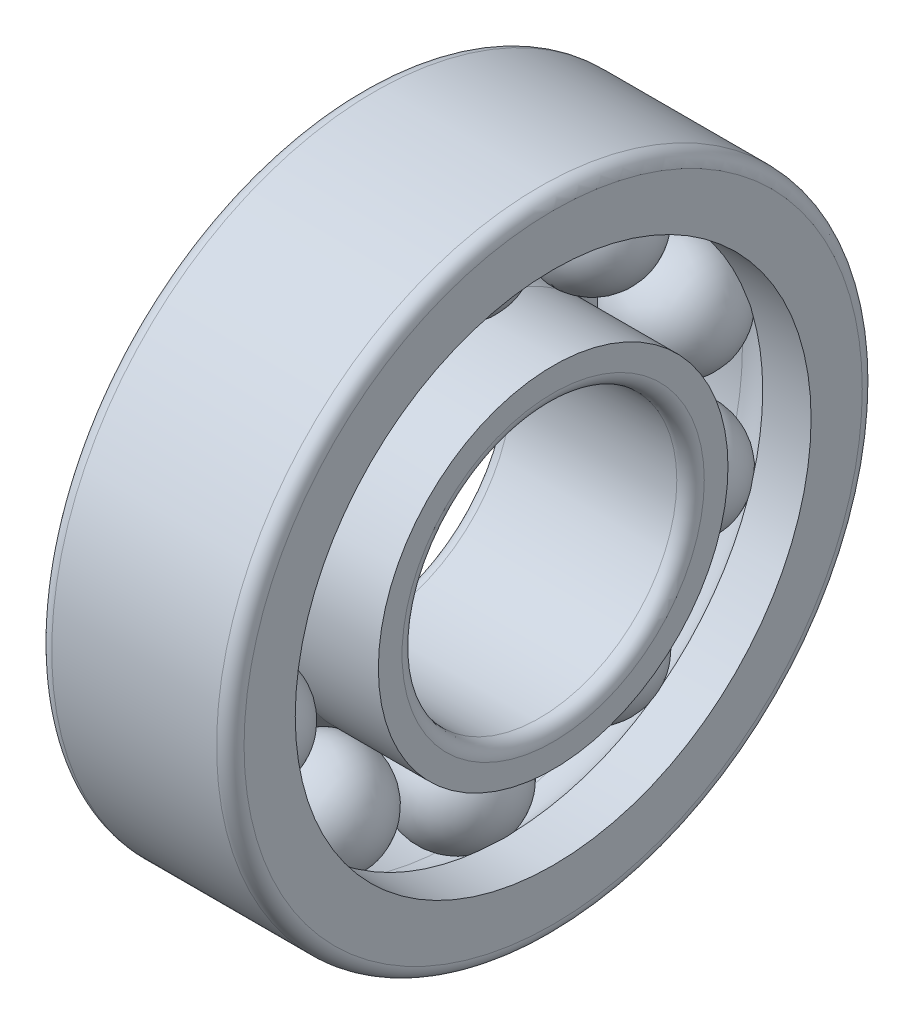
SolidWorks part; units mm, degrees
ref_plane "Plane1" through (0, 0, 0) normal (0, 0, 1) x (1, 0, 0)
ref_plane "Plane2" through (0, 0, 0) normal (0, 1, 0) x (1, 0, 0)
ref_plane "Plane3" through (0, 0, 0) normal (1, 0, 0) x (0, 0, -1)
sketch "Clipboard" plane through (0, 0, 0) normal (0, 0, 1) x (1, 0, 0)
  line L0 (-10, 0) -> (10, 0) construction
  line L1 (0, 0) -> (22.021, -3.8829)
  line L2 (0, 0) -> (16.4955, 2.9086)
  line L3 (0, 0) -> (22.021, -3.8829)
  line L4 (0, 0) -> (-22.3573, -0.3902)
  dimension "BallCLRad" = 16.75
sketch "CagSpiSke" plane through (0, 0, 0) normal (0, 0, 1) x (1, 0, 0)
  line L0 (0.405, 16.075) -> (0.405, 17.425)
  line L1 (0.405, 17.425) -> (-0.405, 17.425)
  line L2 (-0.405, 17.425) -> (-0.405, 16.075)
  line L3 (-0.405, 16.075) -> (0.405, 16.075)
  line L4 (-20.6375, 0) -> (20.6375, 0) construction
  line L5 (0, 0) -> (0, 23.7692) construction
  dimension "OD" = 34.85
  dimension "ID" = 32.15
revolve "CageSpine" add sketch "CagSpiSke" angle 0.001 about L4 reverse direction yes
ref_axis "Axis1" through (-50, 0, 0) along (1, 0, 0)
sketch "CagBalSke" plane through (0, 0, 0) normal (0, 0, 1) x (1, 0, 0)
  line L0 (-4.455, 16.75) -> (4.455, 16.75)
  line L1 (-1.905, 16.75) -> (1.905, 16.75) construction
  line L2 (-10, 0) -> (10, 0) construction
  line L3 (0, 0) -> (0, 24) construction
  arc A0 (4.455, 16.75) -> (-4.455, 16.75) centre (0, 16.75) cw
  dimension "BallCLRad" = 16.75
revolve "CageBall" [suppressed] add sketch "CagBalSke" angle 360 about L1 reverse direction yes
pattern_circular "CageBalls" [suppressed] count 10 every 36 about axis through (-50, 0, 0) along (1, 0, 0)
sketch "CagTrmODSke" plane through (0, 0, 0) normal (0, 0, 1) x (1, 0, 0)
  line L0 (4.456, 17.425) -> (4.456, 21.206)
  line L1 (4.456, 21.206) -> (-4.456, 21.206)
  line L2 (-4.456, 21.206) -> (-4.456, 17.425)
  line L3 (-4.456, 17.425) -> (4.456, 17.425)
  line L4 (-20.6375, 0) -> (20.6375, 0) construction
  line L5 (0, 0) -> (0, 25) construction
  dimension "Width" = 8.912
  dimension "ID" = 34.85
  dimension "OD" = 42.412
revolve "CageTrimOD" [suppressed] cut sketch "CagTrmODSke" angle 360 about L4 reverse direction yes
sketch "CagTrmIDSke" plane through (0, 0, 0) normal (0, 0, 1) x (1, 0, 0)
  line L0 (4.456, 12.296) -> (4.456, 16.075)
  line L1 (4.456, 16.075) -> (-4.456, 16.075)
  line L2 (-4.456, 16.075) -> (-4.456, 12.296)
  line L3 (-4.456, 12.296) -> (4.456, 12.296)
  line L4 (-20.6375, 0) -> (20.6375, 0) construction
  line L5 (0, 0) -> (0, 25) construction
  dimension "Width" = 8.912
  dimension "ID" = 24.592
  dimension "OD" = 32.15
revolve "CageTrimID" [suppressed] cut sketch "CagTrmIDSke" angle 360 about L4 reverse direction yes
sketch "BalSimSke" plane through (0, 0, 0) normal (0, 0, 1) x (1, 0, 0)
  line L0 (-10, 0) -> (10, 0) construction
  line L1 (-10, 16.75) -> (10, 16.75) construction
  line L2 (0, 0) -> (0, 23) construction
  circle A0 centre (0, 16.75) radius 4.05
  dimension "BallCLRad" = 16.75
  dimension "Ball_diameter" = 8.1
revolve "BallsSimplified" [suppressed] add sketch "BalSimSke" angle 360 about L0
sketch "BalDetSke" plane through (0, 0, 0) normal (0, 0, 1) x (1, 0, 0)
  line L0 (-4.05, 16.75) -> (4.05, 16.75)
  line L1 (-1.905, 16.75) -> (1.905, 16.75) construction
  line L2 (0, 0) -> (0, 25) construction
  arc A0 (4.05, 16.75) -> (-4.05, 16.75) centre (0, 16.75) cw
  dimension "BallCLRad" = 16.75
  dimension "Ball_diameter" = 8.1
revolve "BallDetailed" add sketch "BalDetSke" angle 360 about L1 reverse direction yes
sketch "InnRacSke" plane through (0, 0, 0) normal (0, 0, 1) x (1, 0, 0)
  line L0 (-3.4785, 14.725) -> (-7, 14.725)
  line L1 (-7, 14.725) -> (-7, 11)
  line L2 (-6, 10) -> (6, 10)
  line L3 (7, 11) -> (7, 12.725)
  line L4 (0, 12.725) -> (7, 12.725)
  line L5 (-20.6375, 0) -> (20.6375, 0) construction
  line L6 (0, 0) -> (0, 30) construction
  arc A0 (-7, 11) -> (-6, 10) centre (-6, 11) ccw
  arc A1 (6, 10) -> (7, 11) centre (6, 11) ccw
  arc A2 (0, 12.725) -> (-3.4785, 14.725) centre (0, 16.75) cw
  dimension "BallCLRad" = 16.75
  dimension "Fillet_radius" = 1
  dimension "Ball_diameter" = 8.05
  dimension "ID" = 20
  dimension "OD" = 29.45
  dimension "Width" = 14
revolve "InnerRace" add sketch "InnRacSke" angle 360 about L5 reverse direction yes
sketch "OutRacSke" plane through (0, 0, 0) normal (0, 0, 1) x (1, 0, 0)
  line L0 (0, 20.775) -> (-7, 20.775)
  line L1 (-7, 20.775) -> (-7, 22.5)
  line L2 (-6, 23.5) -> (6, 23.5)
  line L3 (7, 22.5) -> (7, 18.775)
  line L4 (7, 18.775) -> (3.4785, 18.775)
  line L5 (-20.6375, 0) -> (20.6375, 0) construction
  line L6 (0, 0) -> (0, 30) construction
  arc A0 (-7, 22.5) -> (-6, 23.5) centre (-6, 22.5) cw
  arc A1 (6, 23.5) -> (7, 22.5) centre (6, 22.5) cw
  arc A2 (3.4785, 18.775) -> (0, 20.775) centre (0, 16.75) ccw
  dimension "BallCLRad" = 16.75
  dimension "Fillet_radius" = 1
  dimension "Ball_diameter" = 8.05
  dimension "Width" = 14
revolve "OuterRace" add sketch "OutRacSke" angle 360 about L5 reverse direction yes
pattern_circular "BallsDetailed" count 10 every 36 about axis through (-50, 0, 0) along (1, 0, 0) of "BallDetailed"
equation "\"BallCLRad@Clipboard\" = ( \"OD@OutRacSke\" + \"ID@InnRacSke\" ) / 4"
equation "\"BallCLRad@BalSimSke\" = \"BallCLRad@Clipboard\""
equation "\"BallCLRad@BalDetSke\" = \"BallCLRad@Clipboard\""
equation "\"BallCLRad@InnRacSke\" = \"BallCLRad@Clipboard\""
equation "\"BallCLRad@OutRacSke\" = \"BallCLRad@Clipboard\""
equation "\"Ball_diameter@InnRacSke\" = \"Ball_diameter@BalDetSke\" - 0.05"
equation "\"Ball_diameter@OutRacSke\" = \"Ball_diameter@BalDetSke\" - 0.05"
equation "\"Ball_diameter@BalSimSke\" = \"Ball_diameter@BalDetSke\""
equation "\"Width@OutRacSke\" = \"Width@InnRacSke\""
equation "\"Fillet_radius@OutRacSke\" = \"Fillet_radius@InnRacSke\""
equation "\"Max_count@Clipboard\" = int( 3.14159265 / atn(( \"Ball_diameter@BalDetSke\" / 2) / sqr( \"BallCLRad@Clipboard\"  *  \"BallCLRad@Clipboard\" - ( \"Ball_diameter@BalDetSke\" / 2) *  ( \"Ball_diameter@BalDetSke\" / 2))))"
equation "\"Max_count@Clipboard\" = ((sgn( \"Max_count@Clipboard\" - \"Count@Clipboard\" )-1)*( \"Max_count@Clipboard\" - \"Count@Clipboard\" ))/-2+ \"Count@Clipboard\""
equation "\"Count@BallsDetailed\" = int( \"Show_count@Clipboard\" ) "
equation "\"Count@BallsDetailed\" = ((sgn( \"Count@BallsDetailed\" - \"Max_count@Clipboard\" )-1)*( \"Count@BallsDetailed\" - \"Max_count@Clipboard\" ))/-2+ \"Max_count@Clipboard\""
equation "\"Count@BallsDetailed\" = ((sgn( \"Count@BallsDetailed\" - \"Min_count@Clipboard\" )+1)*( \"Count@BallsDetailed\" - \"Min_count@Clipboard\"))/2 +\"Min_count@Clipboard\""
equation "\"Angle@BallsDetailed\" = 360.0 / \"Max_count@Clipboard\""
equation "\"BallCLRad@CagBalSke\" = \"BallCLRad@Clipboard\""
equation "\"Count@CageBalls\" = \"Count@BallsDetailed\""
equation "\"Angle@CageBalls\" = \"Angle@BallsDetailed\""
equation "\"Angle@CageSpine\" =  \"Angle@CageBalls\" * ( \"Count@CageBalls\" -1 + int( \"Count@CageBalls\" / \"Max_count@Clipboard\" ) )  + 0.001 -  int( \"Count@CageBalls\" / \"Max_count@Clipboard\" ) * 0.001"
equation "\"Angle@CageSpine\" =  \"Angle@CageSpine\" * int( \"Min_count@Clipboard\" / 2) + int(1 / \"Min_count@Clipboard\")  * 0.001"
equation "\"CageWallOD@CagBalSke\" =  \"Ball_diameter@BalDetSke\" * 1.1"
equation "\"Thickness@CagSpiSke\" =  \"Ball_diameter@BalDetSke\" * 0.1"
equation "\"OD@CagTrmODSke\" = \"BallCLRad@Clipboard\" * 2 + \"CageWallOD@CagBalSke\" + 0.002"
equation "\"ID@CagTrmODSke\" = \"BallCLRad@Clipboard\" * 2 + \"Ball_diameter@BalDetSke\" / 6"
equation "\"OD@CagTrmIDSke\" = \"BallCLRad@Clipboard\" * 2 - \"Ball_diameter@BalDetSke\" / 6"
equation "\"ID@CagTrmIDSke\" = \"BallCLRad@Clipboard\" * 2 - \"CageWallOD@CagBalSke\" + 0.002"
equation "\"OD@CagSpiSke\" = \"ID@CagTrmODSke\""
equation "\"ID@CagSpiSke\" = \"OD@CagTrmIDSke\""
equation "\"Width@CagTrmODSke\" = \"CageWallOD@CagBalSke\" + 0.002"
equation "\"Width@CagTrmIDSke\" = \"CageWallOD@CagBalSke\" + 0.002"
